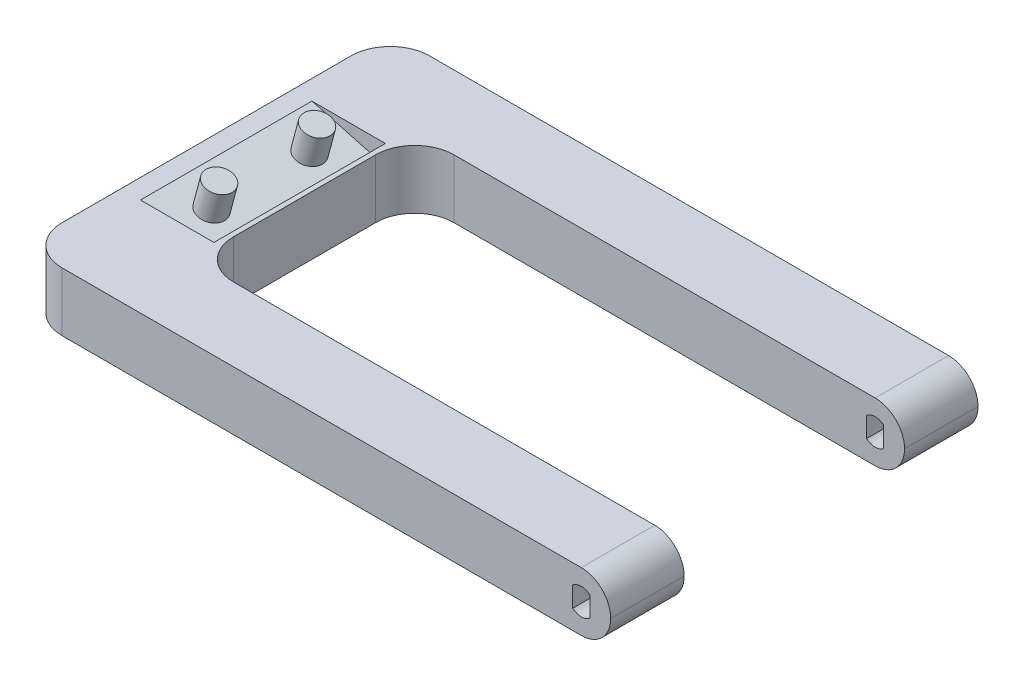
SolidWorks part; units mm, degrees
ref_plane "Front" through (0, 0, 0) normal (0, 0, 1) x (1, 0, 0)
ref_plane "Top" through (0, 0, 0) normal (0, 1, 0) x (1, 0, 0)
ref_plane "Right" through (0, 0, 0) normal (1, 0, 0) x (0, 0, -1)
sketch "Sketch1" plane through (0, 0, 0) normal (0, 1, 0) x (1, 0, 0)
  line L0 (50, 37.5) -> (50, 22.5)
  line L1 (50, 22.5) -> (-50, 22.5)
  line L2 (-50, 22.5) -> (-50, -22.5)
  line L3 (-50, -22.5) -> (50, -22.5)
  line L4 (50, -22.5) -> (50, -37.5)
  line L5 (50, -37.5) -> (-70, -37.5)
  line L6 (-70, -37.5) -> (-70, 37.5)
  line L7 (-70, 37.5) -> (50, 37.5)
  point P2 (-50, 0)
  point P9 (0, -22.5)
  dimension "D1" = 15
  dimension "D2" = 20
  dimension "D3" = 120
  dimension "D4" = 45
extrude "Boss-Extrude1" add sketch "Sketch1" along normal mid plane 12
fillet "Fillet1" radius 6 4 edges at (50, 6, -30) (50, -6, -30) (50, -6, 30) (50, 6, 30)
fillet "Fillet2" radius 8 4 edges at (-70, 0, -37.5) (-70, 0, 37.5) (-50, 0, -22.5) (-50, 0, 22.5)
hole_wizard "Ø6.0mm Dowel Hole1" [suppressed] positions "Sketch2" profile "Sketch3" hole size "Ø6.0" standard "ANSI Metric"
sketch "Sketch2" plane through (0, 0, 57.5) normal (0, 0, 1) x (1, 0, 0)
  point P0 (37.5, 0)
sketch "Sketch3" plane through (37.5, 0, 57.5) normal (1, 0, 0) x (0, -1, 0)
  line L0 (0, 0) -> (0, 115)
  line L1 (0, 115) -> (3, 115)
  line L2 (3, 115) -> (3, 0)
  line L5 (3, 0) -> (0, 0)
  line L11 (0, -6.35) -> (0, 107.95) construction
  dimension "Thru Hole Dia." = 6
  dimension "Thru Hole Depth" = 115
ref_plane "Plane1" [suppressed] through (0, 0, 12.5) normal (0, 0, 1) x (1, 0, 0)
sketch "Sketch4" plane through (0, 0, 0) normal (0, 0, 1) x (1, 0, 0)
  line L0 (-66, 6) -> (-51, 1.9808)
  line L1 (-51, 1.9808) -> (-51, 6)
  line L2 (-62, 6) -> (44, 6) construction
  line L3 (-51, 6) -> (-66, 6)
  line L4 (-62, 6) -> (-70, 6) construction
  dimension "D1" = 15
  dimension "D2" = 15
extrude "Cut-Extrude1" cut sketch "Sketch4" against normal mid plane 35
sketch "Sketch5" plane through (-2.9212, -10.9019, 0) normal (0.2588, 0.9659, 0) x (0.9659, -0.2588, 0)
  line L2 (-50.8151, 17.5) -> (-65.304, 17.5) construction
  line L3 (-58.0596, 10) -> (-58.0596, -10) construction
  line L4 (-65.304, 17.5) -> (-65.304, -17.5) construction
  circle A0 centre (-58.0596, 10) radius 2.75
  circle A1 centre (-58.0596, -10) radius 2.75
  point P4 (-58.0596, 0)
  point P9 (-58.0596, 17.5)
  point P10 (-65.304, 0)
  dimension "D1" = 5.5
  dimension "D2" = 5.5
  dimension "D3" = 20
extrude "Boss-Extrude2" add sketch "Sketch5" along normal blind 6
sketch "Sketch6" plane through (0, 0, 37.5) normal (0, 0, 1) x (1, 0, 0)
  line L0 (42.25, -2.0561) -> (42.25, 2.0561)
  line L1 (45.75, 2.0561) -> (45.75, -2.0561)
  line L2 (42.25, 0) -> (45.75, 0) construction
  arc A0 (42.25, -2.0561) -> (45.75, -2.0561) centre (44, 0) ccw
  arc A1 (45.75, 2.0561) -> (42.25, 2.0561) centre (44, 0) ccw
  point P1 (0, 0)
  point P9 (44, 0)
  dimension "D1" = 5.4
  dimension "D2" = 3.5
extrude "Cut-Extrude2" cut sketch "Sketch6" against normal through all
